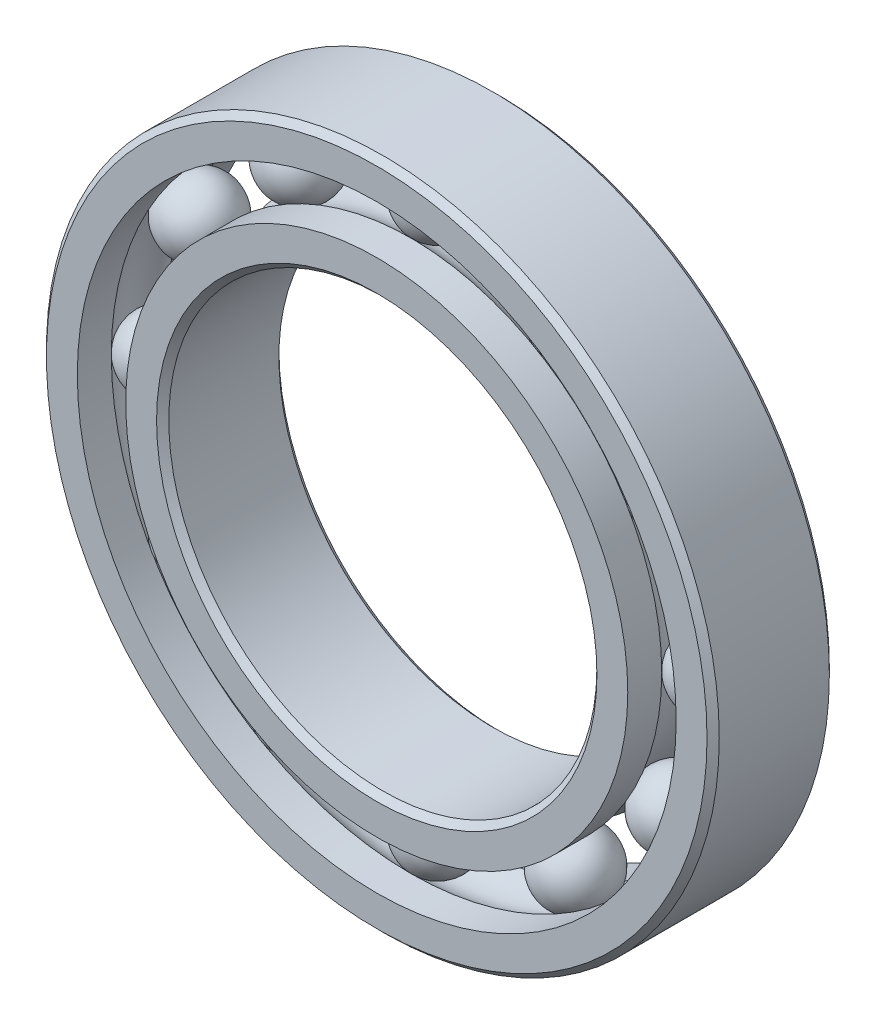
SolidWorks part; units mm, degrees
ref_plane "Front Plane" through (0, 0, 0) normal (0, 0, 1) x (1, 0, 0)
ref_plane "Top Plane" through (0, 0, 0) normal (0, 1, 0) x (1, 0, 0)
ref_plane "Right Plane" through (0, 0, 0) normal (1, 0, 0) x (0, 0, -1)
sketch "Sketch1" plane through (0, 0, 0) normal (1, 0, 0) x (0, 0, -1)
  line L0 (-5, 0) -> (5, 0) construction
  line L1 (0, 27.5) -> (0, -27.5) construction
  line L2 (4.5, 27.5) -> (-4.5, 27.5)
  line L3 (-4.5, 27.5) -> (-5, 27)
  line L4 (-5, 27) -> (-5, 24.4778)
  line L5 (-5, 24.4778) -> (-2.2222, 24.4778)
  line L6 (5, 24.4778) -> (2.2222, 24.4778)
  line L7 (5, 27) -> (5, 24.4778)
  line L8 (4.5, 27.5) -> (5, 27)
  line L9 (0, 27.5) -> (0, 22.4997) construction
  line L10 (0, 22.4997) -> (0, 17.4995) construction
  arc A0 (-2.2222, 24.4778) -> (2.2222, 24.4778) centre (0, 22.4997) cw
  point P14 (0, 17.4995)
  dimension "Width" = 10
  dimension "OD" = 55
  dimension "D1" = 45
  dimension "D2" = 0.5
  dimension "Shaft Dia" = 34.999
  dimension "D3" = 4.4444
  dimension "D4" = 1.978
revolve "Revolve1" add sketch "Sketch1" angle 360 about L0
sketch "Sketch3" plane through (0, 0, 0) normal (1, 0, 0) x (0, 0, -1)
  line L0 (-5, 20.5217) -> (-2.2222, 20.5217)
  line L1 (0, 27.5) -> (0, -27.5) construction
  line L2 (-5, 27) -> (-5, 24.4778) construction
  line L3 (-5, 20.5217) -> (-5, 17.9995)
  line L4 (-4.5, 27.5) -> (-5, 27) construction
  line L5 (-5, 17.9995) -> (-4.5, 17.4995)
  line L6 (-4.5, 17.4995) -> (4.5, 17.4995)
  line L7 (4.5, 27.5) -> (4.5, -27.5) construction
  line L8 (4.5, 17.4995) -> (5, 17.9995)
  line L9 (5, -27) -> (5, 27) construction
  line L10 (5, 17.9995) -> (5, 20.5217)
  line L11 (5, 20.5217) -> (2.2222, 20.5217)
  line L13 (4.5, 27.5) -> (5, 27) construction
  arc A0 (2.2222, 24.4778) -> (-2.2222, 24.4778) centre (0, 22.4997) ccw construction
  arc A1 (2.2222, 20.5217) -> (-2.2222, 20.5217) centre (0, 22.4997) cw
revolve "Revolve3" add sketch "Sketch3" angle 360 about L0
sketch "Sketch4" plane through (0, 0, 0) normal (1, 0, 0) x (0, 0, -1)
  line L0 (-2.975, 22.4997) -> (2.975, 22.4997)
  arc A2 (-2.975, 22.4997) -> (2.975, 22.4997) centre (0, 22.4997) cw
  arc A3 (2.2222, 24.4778) -> (-2.2222, 24.4778) centre (0, 22.4997) ccw construction
revolve "Revolve4" add sketch "Sketch4" angle 360 about L0
ref_axis "Axis1" through (0, 0, -5) along (0, 0, 1)
pattern_circular "CirPattern1" count 12 every 30 about axis through (0, 0, -5) along (0, 0, 1) of bodies 104
sketch "Sketch5" plane through (0, 0, 0) normal (1, 0, 0) x (0, 0, -1)
  line L0 (-5, 24.4778) -> (-2.2222, 24.4778) construction
  line L1 (-4.75, 24.4778) -> (-2.975, 24.4778)
  line L2 (-4.75, 24.4778) -> (-4.75, 20.5217)
  line L3 (-4.75, 20.5217) -> (-2.975, 20.5217)
  line L4 (-2.975, 24.4778) -> (-2.975, 20.5217)
  line L5 (-5, 20.5217) -> (-2.2222, 20.5217) construction
  line L6 (5, 24.4778) -> (2.2222, 24.4778) construction
  line L7 (4.75, 24.4778) -> (2.975, 24.4778)
  line L8 (4.75, 24.4778) -> (4.75, 20.5217)
  line L9 (4.75, 20.5217) -> (2.975, 20.5217)
  line L10 (2.975, 24.4778) -> (2.975, 20.5217)
  line L11 (5, 20.5217) -> (2.2222, 20.5217) construction
  line L12 (-4.5, 27.5) -> (-5, 27) construction
  point P18 (-4.75, 27.25)
equation "\"D2@Sketch1\" = \"Width@Sketch1\"*.05"
equation "\"D3@Sketch1\" = \"Width@Sketch1\"/2.25"
equation "\"D4@Sketch1\" = (((\"OD@Sketch1\"-\"Width@Sketch1\")/2)/3.25)/3.5"
equation "\"D2@CirPattern1\" = 360/\"Balls@CirPattern1\""
